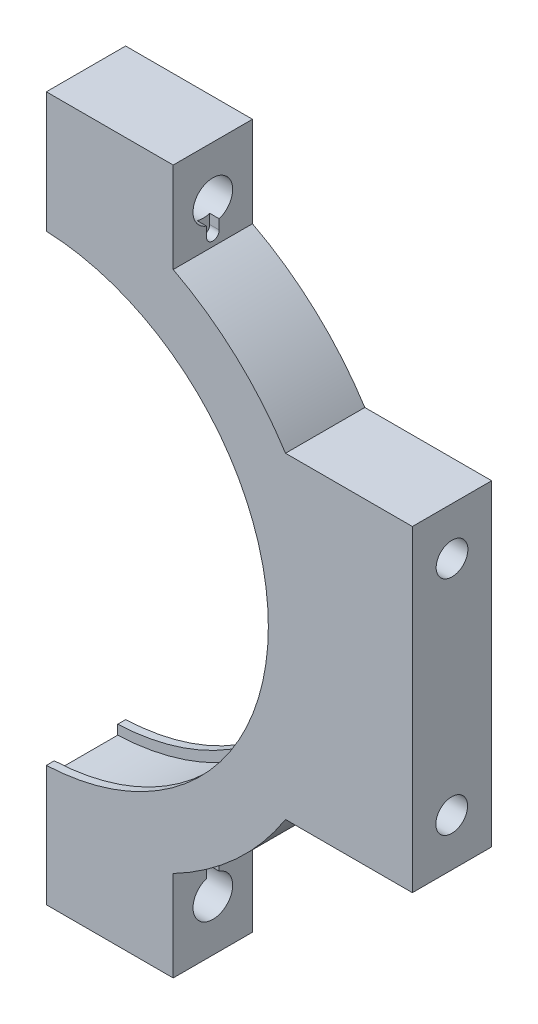
SolidWorks part; units mm, degrees
material "Tungsten"
ref_plane "Front Plane" through (0, 0, 0) normal (0, 0, 1) x (1, 0, 0)
ref_plane "Top Plane" through (0, 0, 0) normal (0, 1, 0) x (1, 0, 0)
ref_plane "Right Plane" through (0, 0, 0) normal (1, 0, 0) x (0, 0, -1)
sketch "Sketch1" plane through (0, 0, 0) normal (0, 0, 1) x (1, 0, 0)
  line L0 (0, 0) -> (-50000, 0) construction
  line L1 (0, 0) -> (0, -50000) construction
  line L2 (3, -72.9383) -> (3, -111)
  line L3 (3, -111) -> (43, -111)
  line L4 (43, -111) -> (43, -82.4621)
  line L5 (3, 72.9383) -> (3, 111)
  line L6 (3, 111) -> (43, 111)
  line L7 (43, 111) -> (43, 82.4621)
  line L8 (78.4156, 50) -> (118.4156, 50)
  line L9 (78.4156, -50) -> (118.4156, -50)
  line L10 (118.4156, 50) -> (118.4156, -50)
  line L11 (3, -2.062) -> (3, -50002.062) construction
  arc A0 (43, -82.4621) -> (78.4156, -50) centre (0, 0) ccw
  arc A1 (3, -72.9383) -> (3, 72.9383) centre (0, 0) ccw
  arc A2 (3, -75.9408) -> (3, 75.9408) centre (0, 0) ccw
  arc A3 (78.4156, 50) -> (43, 82.4621) centre (0, 0) ccw
  point P7 (0, 0)
  point P20 (8.8455, -103.1906)
  point P22 (0, 0)
  point P23 (0, 0)
  point P24 (5.245, -72.8113)
  point P25 (0, 0)
  point P26 (0, 0)
  point P27 (0, 0)
  point P30 (3, 0)
  point P31 (3, 0)
  point P32 (0, 0)
  point P33 (0, 0)
  point P34 (0, -11.178)
  point P35 (0, 0)
  dimension "D1" = 76
  dimension "D2" = 73
  dimension "D8" = 93
  dimension "D3" = 222
  dimension "D4" = 40
  dimension "D5" = 100
  dimension "D6" = 40
  dimension "D7" = 3
extrude "Boss-Extrude1" add sketch "Sketch1" along normal blind 25 contours L8 A3 L7 L6 L5 A2 L2 L3 L4 A0 L9 L10 | L2 A2 L5 A1 region at (74.6851, 0, 0) region at (78.5021, 0, 0)
sketch "Sketch2" plane through (43, 0, 0) normal (1, 0, 0) x (0, 0, -1)
  line L0 (-14.5, -86) -> (-14.5, -89.0786)
  line L1 (-10.5, -86) -> (-10.5, -89.0786)
  line L2 (-25, 111) -> (0, 111)
  line L3 (0, 0) -> (-50000, 0) construction
  line L4 (0, 0) -> (0, 49790.6164) construction
  line L6 (-10.5, 86) -> (-10.5, 89.0786)
  line L7 (-14.5, 86) -> (-14.5, 89.0786)
  circle A0 centre (-12.5, 95) radius 6.25
  circle A1 centre (-12.5, -95) radius 6.25
  arc A2 (-14.5, 86) -> (-10.5, 86) centre (-12.5, 86) ccw
  arc A3 (-14.5, -86) -> (-10.5, -86) centre (-12.5, -86) cw
  circle A4 centre (-12.5, -95) radius 6.25
  point P5 (-12.5, 111)
  dimension "D1" = 12.5
  dimension "D3" = 4
  dimension "D2" = 190
  dimension "D4" = 9
hole_wizard "Ø10.0mm Dowel Hole1" positions "3DSketch1" profile "Sketch3" hole size "Ø10.0" standard "ANSI Metric"
sketch3d "3DSketch1"
  line L0 (118.4156, 50, 25) -> (118.4156, 50, 0)
  point P0 (118.4156, 35, 12.5)
  point P2 (118.4156, -34.9999, 12.6004)
  point P11 (118.4156, 50, 12.5)
  dimension "D1" = 70
  dimension "D2" = 15
sketch "Sketch3" plane through (118.4156, 35, 12.5) normal (0, 1, 0) x (0, 0, -1)
  line L0 (0, 0) -> (0, 28.0043)
  line L1 (0, 28.0043) -> (5, 25)
  line L2 (5, 25) -> (5, 0)
  line L5 (5, 0) -> (0, 0)
  line L10 (0, 28.0043) -> (-5, 25) construction
  line L11 (0, -6.35) -> (0, 107.95) construction
  dimension "Hole Dia." = 10
  dimension "Hole Depth" = 25
  dimension "Drill Angle" = 118
extrude "Cut-Extrude2" cut sketch "Sketch2" against normal through all contours A0 | A1 L2 region at (43, -95, 12.5) region at (43, 95, 12.5)
extrude "Cut-Extrude3" cut sketch "Sketch2<4>" against normal blind 3 contours L7 A2 L6 A0 | A3 L0 A1 L1 region at (43, -86.6224, 12.5) region at (43, 86.6224, 12.5)
sketch "Sketch2<4>" plane through (43, 0, 0) normal (1, 0, 0) x (0, 0, -1) same geometry as "Sketch2"
extrude "Cut-Extrude4" cut sketch "Sketch1<3>" along normal blind 20 from offset 2.5 contours L2 A2 L5 A1 region at (74.6851, 0, 0)
sketch "Sketch1<3>" plane through (0, 0, 0) normal (0, 0, 1) x (1, 0, 0) same geometry as "Sketch1"
